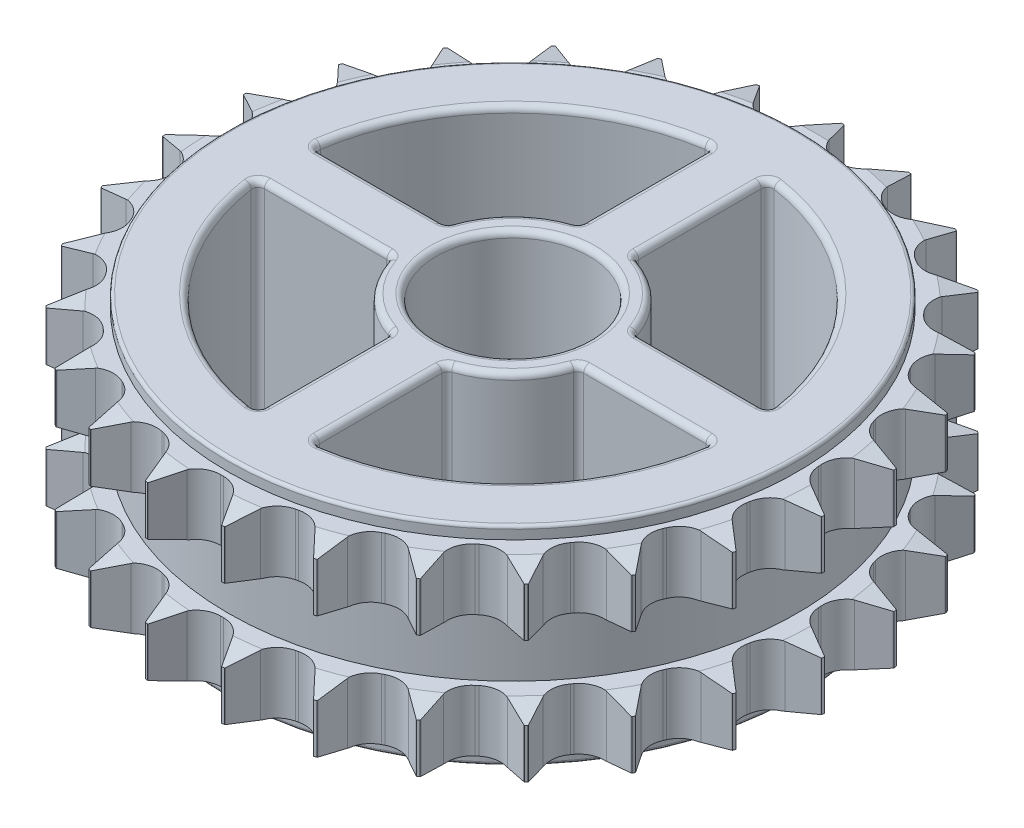
SolidWorks part; units mm, degrees
ref_plane "Front Plane" through (0, 0, 0) normal (0, 0, 1) x (1, 0, 0)
ref_plane "Top Plane" through (0, 0, 0) normal (0, 1, 0) x (1, 0, 0)
ref_plane "Right Plane" through (0, 0, 0) normal (1, 0, 0) x (0, 0, -1)
sketch "Sketch1" plane through (0, 0, 0) normal (0, 1, 0) x (1, 0, 0)
  line L0 (3, 47.4052) -> (0, 54.5)
  line L1 (0, 54.5) -> (-3, 47.4052)
  line L2 (0, 54.5) -> (0, 47.5) construction
  line L3 (-3, 47.4052) -> (0, 47.5) construction
  line L4 (0, 47.5) -> (3, 47.4052) construction
  line L5 (-3, 47.4052) -> (0, 47.5) construction
  line L6 (0, 47.5) -> (3, 47.4052) construction
  line L7 (13.8515, 45.4355) -> (12.5686, 53.0309)
  line L8 (12.5686, 53.0309) -> (8.0132, 46.8192)
  line L9 (23.9563, 41.0164) -> (24.4596, 48.703)
  line L10 (24.4596, 48.703) -> (18.5945, 43.7092)
  line L11 (32.7696, 34.3861) -> (35.0319, 41.7494)
  line L12 (35.0319, 41.7494) -> (28.1733, 38.2428)
  line L13 (39.8163, 25.902) -> (43.7157, 32.5451)
  line L14 (43.7157, 32.5451) -> (36.2333, 30.7148)
  line L15 (44.7164, 16.0216) -> (50.0428, 21.5863)
  line L16 (50.0428, 21.5863) -> (42.3399, 21.5309)
  line L17 (47.2059, 5.2774) -> (53.672, 9.4638)
  line L18 (53.672, 9.4638) -> (46.164, 11.1862)
  line L19 (47.1505, -5.7513) -> (54.4078, -3.1689)
  line L20 (54.4078, -3.1689) -> (47.4994, 0.2386)
  line L21 (44.5532, -16.4699) -> (52.2104, -15.6308)
  line L22 (52.2104, -15.6308) -> (46.2741, -10.722)
  line L23 (39.5541, -26.3007) -> (47.1984, -27.25)
  line L24 (47.1984, -27.25) -> (42.5541, -21.1045)
  line L25 (32.4225, -34.7135) -> (39.6419, -37.4002)
  line L26 (39.6419, -37.4002) -> (36.54, -30.3493)
  line L27 (23.5431, -41.255) -> (29.9482, -45.5341)
  line L28 (29.9482, -45.5341) -> (28.556, -37.9579)
  line L29 (13.3944, -45.5723) -> (18.6401, -51.2132)
  line L30 (18.6401, -51.2132) -> (19.0326, -43.5202)
  line L31 (2.5237, -47.4329) -> (6.3271, -54.1315)
  line L32 (6.3271, -54.1315) -> (8.4831, -46.7364)
  line L33 (-8.4831, -46.7364) -> (-6.3271, -54.1315)
  line L34 (-6.3271, -54.1315) -> (-2.5237, -47.4329)
  line L35 (-19.0326, -43.5202) -> (-18.6401, -51.2132)
  line L36 (-18.6401, -51.2132) -> (-13.3944, -45.5723)
  line L37 (-28.556, -37.9579) -> (-29.9482, -45.5341)
  line L38 (-29.9482, -45.5341) -> (-23.5431, -41.255)
  line L39 (-36.54, -30.3493) -> (-39.6419, -37.4002)
  line L40 (-39.6419, -37.4002) -> (-32.4225, -34.7135)
  line L41 (-42.5541, -21.1045) -> (-47.1984, -27.25)
  line L42 (-47.1984, -27.25) -> (-39.5541, -26.3007)
  line L43 (-46.2741, -10.722) -> (-52.2104, -15.6308)
  line L44 (-52.2104, -15.6308) -> (-44.5532, -16.4699)
  line L45 (-47.4994, 0.2386) -> (-54.4078, -3.1689)
  line L46 (-54.4078, -3.1689) -> (-47.1505, -5.7513)
  line L47 (-46.164, 11.1862) -> (-53.672, 9.4638)
  line L48 (-53.672, 9.4638) -> (-47.2059, 5.2774)
  line L49 (-42.3399, 21.5309) -> (-50.0428, 21.5863)
  line L50 (-50.0428, 21.5863) -> (-44.7164, 16.0216)
  line L51 (-36.2333, 30.7148) -> (-43.7157, 32.5451)
  line L52 (-43.7157, 32.5451) -> (-39.8163, 25.902)
  line L53 (-28.1733, 38.2428) -> (-35.0319, 41.7494)
  line L54 (-35.0319, 41.7494) -> (-32.7696, 34.3861)
  line L55 (-18.5945, 43.7092) -> (-24.4596, 48.703)
  line L56 (-24.4596, 48.703) -> (-23.9563, 41.0164)
  line L57 (-8.0132, 46.8192) -> (-12.5686, 53.0309)
  line L58 (-12.5686, 53.0309) -> (-13.8515, 45.4355)
  line L59 (0, 16) -> (0, 37.5) construction
  line L60 (-4.5, 37.229) -> (-4.5, 15.3542)
  line L61 (4.5, 37.229) -> (4.5, 15.3542)
  line L62 (37.229, -4.5) -> (15.3542, -4.5)
  line L63 (37.229, 4.5) -> (15.3542, 4.5)
  line L64 (-4.5, -37.229) -> (-4.5, -15.3542)
  line L65 (4.5, -37.229) -> (4.5, -15.3542)
  line L66 (-37.229, 4.5) -> (-15.3542, 4.5)
  line L67 (-37.229, -4.5) -> (-15.3542, -4.5)
  line L69 (-1.7, 1.3964) -> (-1.7, -1.3964)
  circle A0 centre (0, 0) radius 47.5
  circle A1 centre (0, 0) radius 37.5
  circle A2 centre (0, 0) radius 5
  circle A3 centre (0, 0) radius 2.2
  circle A4 centre (0, 0) radius 16
  circle A5 centre (0, 0) radius 46.5
  point P88 (0, 0)
  point P111 (0, 0)
  dimension "D1" = 95
  dimension "D5" = 75
  dimension "D6" = 10
  dimension "D7" = 4.4
  dimension "D8" = 32
  dimension "D9" = 4
  dimension "D11" = 0.5
  dimension "D12" = 1
  dimension "D2" = 7
  dimension "D3" = 3
  dimension "D10" = 9
  dimension "D4" = 27
extrude "Boss-Extrude2" add sketch "Sketch1" along normal blind 10 from offset 2 contours A2 A3 | L69 A3 | A4 A2 | A4 L62 A1 L63 | A4 L64 A1 L65 | A4 L66 A1 L67 | A4 L61 A1 L60 | A5 A1 | A0 | L69 A3 region at (5.4988, 0, -47.0454) region at (0, 0, -26.5974) region at (0, 0, -15.5475) region at (-26.5974, 0, 0) region at (26.5974, 0, 0) region at (0, 0, 26.5974) region at (0.1274, 0, 0) region at (-1.9021, 0, 0) region at (-4.8586, 0, 0) region at (-45.1848, 0, 0)
extrude "Boss-Extrude3" add sketch "Sketch1<7>" along normal blind 22 contours L69 A3 | A5 A1 | A4 A2 | A2 A3 | A4 L66 A1 L67 | A4 L64 A1 L65 | A4 L62 A1 L63 | A4 L61 A1 L60 | A3 region at (0, 0, -26.5974) region at (0, 0, -15.5475) region at (-26.5974, 0, 0) region at (26.5974, 0, 0) region at (0, 0, 26.5974) region at (-1.9021, 0, 0) region at (-4.8586, 0, 0) region at (-45.1848, 0, 0)
sketch "Sketch1<7>" plane through (0, 0, 0) normal (0, 1, 0) x (1, 0, 0) same geometry as "Sketch1"
extrude "Boss-Extrude4" add sketch "Sketch1<8>" along normal blind 10 from surface contours A4 A2 | A2 A3 | L69 A3 | A4 L62 A1 L63 | A4 L64 A1 L65 | A4 L66 A1 L67 | A4 L61 A1 L60 | A5 A1 | A0 region at (5.4988, 0, -47.0454) region at (0, 0, -26.5974) region at (0, 0, -15.5475) region at (-26.5974, 0, 0) region at (26.5974, 0, 0) region at (0, 0, 26.5974) region at (-1.9021, 0, 0) region at (-4.8586, 0, 0) region at (-45.1848, 0, 0) starting at face at (-17.1554, 22, 17.1554)
sketch "Sketch1<8>" plane through (0, 0, 0) normal (0, 1, 0) x (1, 0, 0) same geometry as "Sketch1"
extrude "Boss-Extrude6" add sketch "Sketch1<10>" along normal blind 10 from offset 2 contours A0 L57 L58 region at (-11.4875, 0, -48.4696)
sketch "Sketch1<10>" plane through (0, 0, 0) normal (0, 1, 0) x (1, 0, 0) same geometry as "Sketch1"
extrude "Boss-Extrude7" add sketch "Sketch1<12>" along normal blind 10 from surface contours A0 L57 L58 region at (-11.4875, 0, -48.4696) starting at face at (0, 22, 47.5)
sketch "Sketch1<12>" plane through (0, 0, 0) normal (0, 1, 0) x (1, 0, 0) same geometry as "Sketch1"
fillet "Fillet1" radius 4 4 edges at (-13.8515, 7, -45.4355) (-8.0132, 7, -46.8192) (-13.8515, 27, -45.4355) (-8.0132, 27, -46.8192)
fillet "Fillet2" radius 0.3 2 edges at (-12.5686, 7, -53.0309) (-12.5686, 27, -53.0309)
pattern_circular "CirPattern1" count 27 over 360 about axis through (0, 32, 0) along (0, 1, 0) of "Fillet2", "Fillet1", "Boss-Extrude7", "Boss-Extrude6"
sketch "Sketch3" plane through (0, 32, 0) normal (0, 1, 0) x (1, 0, 0)
  circle A0 centre (0, 0) radius 2.5
sketch "Sketch4" plane through (0, 32, 0) normal (0, 1, 0) x (1, 0, 0)
  circle A0 centre (0, 0) radius 0.5
  dimension "D1" = 1
sketch "Sketch6" plane through (0, 32, 0) normal (0, 1, 0) x (1, 0, 0)
  line L0 (-15.3542, 4.5) -> (-37.229, 4.5)
  line L1 (-15.3542, -4.5) -> (-37.229, -4.5)
  line L2 (4.5, 15.3542) -> (4.5, 37.229)
  line L3 (-4.5, 15.3542) -> (-4.5, 37.229)
  line L4 (15.3542, -4.5) -> (37.229, -4.5)
  line L5 (15.3542, 4.5) -> (37.229, 4.5)
  line L6 (-4.5, -15.3542) -> (-4.5, -37.229)
  line L7 (4.5, -15.3542) -> (4.5, -37.229)
  circle A0 centre (0, 0) radius 16
  circle A1 centre (0, 0) radius 46.5
  circle A2 centre (0, 0) radius 37.5
  circle A3 centre (0, 0) radius 16
  circle A4 centre (0, 0) radius 16
  circle A5 centre (0, 0) radius 16
  point P31 (0, 0)
  dimension "D1" = 93
  dimension "D2" = 32
  dimension "D3" = 4
extrude "Boss-Extrude12" add sketch "Sketch6" along normal blind 2 contours L2 A2 L3 A0 | A1 A2 | L0 A2 L1 A0 | L6 A2 L7 A0 | A0 | L4 A2 L5 A0 region at (-26.5974, 32, 0) region at (0, 32, 0) region at (0, 32, -26.5974) region at (0, 32, 26.5974) region at (26.5974, 32, 0) region at (-45.1848, 32, 0)
fillet "Fillet9" radius 0.5 2 edges at (0, 34, 46.5) (0, 0, 46.5)
sketch "Sketch7" plane through (0, 34, 0) normal (0, 1, 0) x (1, 0, 0)
  line L0 (0, 0) -> (0, 5.8384) construction
  line L1 (0, 0) -> (-4.8311, 0) construction
  circle A1 centre (-8, 0) radius 1.5
  circle A2 centre (0, 8) radius 1.5
  circle A3 centre (8, 0) radius 1.5
  circle A4 centre (0, -8) radius 1.5
  point P18 (0, 0)
  dimension "D2" = 3
  dimension "D1" = 90
  dimension "D3" = 8
  dimension "D4" = 4
extrude "Cut-Extrude1" cut sketch "Sketch7" against normal up to next
sketch "Sketch10" plane through (0, 34, 0) normal (0, 1, 0) x (1, 0, 0)
  circle A0 centre (0, 0) radius 12.5
  dimension "D1" = 25
extrude "Cut-Extrude2" cut sketch "Sketch10" against normal offset from surface (21 mm away) 13 up to face at (-8, 0, 1.5)
fillet "Fillet17" radius 1 44 edges at (15.3542, 17, -4.5) (37.229, 17, -4.5) (-4.5, 17, 37.229) (-4.5, 17, 15.3542) (-15.3542, 17, 4.5) (-37.229, 17, 4.5) (-37.229, 17, -4.5) (-15.3542, 17, -4.5) (-4.5, 17, -15.3542) (-4.5, 17, -37.229) (4.5, 17, -37.229) (4.5, 17, -15.3542) (4.5, 17, 15.3542) (4.5, 17, 37.229) (37.229, 17, 4.5) (15.3542, 17, 4.5) (-11.3137, 34, 11.3137) (-26.5165, 34, -26.5165) (-11.3137, 0, 11.3137) (26.5165, 0, 26.5165) (-11.3137, 34, -11.3137) (-11.3137, 0, -11.3137) (11.3137, 34, -11.3137) (26.5165, 34, -26.5165) (11.3137, 0, -11.3137) (11.3137, 34, 11.3137) (11.3137, 0, 11.3137) (26.2916, 34, -4.5) (26.2916, 0, -4.5) (-4.5, 34, 26.2916) (-4.5, 0, 26.2916) (-26.2916, 34, 4.5) (-26.2916, 0, 4.5) (-26.2916, 34, -4.5) (-26.2916, 0, -4.5) (-4.5, 34, -26.2916) (-4.5, 0, -26.2916) (4.5, 34, -26.2916) (4.5, 0, -26.2916) (4.5, 34, 26.2916) (4.5, 0, 26.2916) (26.2916, 34, 4.5) (26.2916, 0, 4.5) (0, 34, 12.5)
sketch "Sketch11" plane through (0, 0, 0) normal (0, 0, 1) x (1, 0, 0)
  line L0 (-49.4165, 12) -> (-53.7394, 12) construction
  line L1 (-53.7394, 2) -> (-49.4165, 2) construction
  line L2 (-49.4165, 2) -> (-49.4165, 12) construction
  line L3 (-53.7394, 12) -> (-53.9388, 12) construction
  line L4 (-53.7715, 12) -> (-53.7715, 2) construction
  line L5 (-53.9388, 2) -> (-53.7394, 2) construction
  line L6 (-53.7394, 32) -> (-53.9388, 32) construction
  line L7 (-53.7715, 32) -> (-53.7715, 22) construction
  line L8 (-53.9388, 22) -> (-53.7394, 22) construction
  line L9 (-49.4165, 32) -> (-53.7394, 32) construction
  line L10 (-53.7394, 22) -> (-49.4165, 22) construction
  line L11 (-49.4165, 22) -> (-49.4165, 32) construction
  line L13 (-49.4165, 12) -> (-53.7394, 12)
  line L14 (-53.7394, 2) -> (-49.4165, 2)
  line L15 (-49.4165, 2) -> (-49.4165, 12)
  line L16 (-53.7394, 12) -> (-53.9388, 12)
  line L17 (-53.7715, 12) -> (-53.7715, 2)
  line L18 (-53.9388, 2) -> (-53.7394, 2)
  line L19 (-53.7394, 32) -> (-53.9388, 32)
  line L20 (-53.7715, 32) -> (-53.7715, 22)
  line L21 (-53.9388, 22) -> (-53.7394, 22)
  line L22 (-49.4165, 32) -> (-53.7394, 32)
  line L23 (-53.7394, 22) -> (-49.4165, 22)
  line L24 (-49.4165, 22) -> (-49.4165, 32)
  line L25 (-53.9388, 32) -> (-53.9388, 22)
  line L26 (-53.9388, 12) -> (-53.9388, 2) construction
  line L27 (-53.9388, 12) -> (-53.9388, 2)
  line L28 (-53.9388, 22) -> (-53.9388, 12) construction
  line L29 (-53.9388, 17) -> (-47.598, 17) construction
  line L30 (-52.955, 27) -> (-56.5762, 27) construction
  line L31 (-49.4165, 32) -> (-53.9388, 31)
  line L32 (-49.4165, 22) -> (-53.9388, 23)
  line L33 (-49.4165, 12) -> (-53.9388, 11)
  line L34 (-49.4165, 2) -> (-53.9388, 3)
  line L35 (0, 27) -> (0, 33.2542) construction
  line L36 (-53.9388, 32) -> (-54.2683, 32)
  line L37 (-53.9388, 31) -> (-54.2683, 31)
  line L38 (-53.9388, 31) -> (-53.9388, 23)
  line L39 (-53.9388, 23) -> (-54.2683, 23)
  line L40 (-54.2683, 31) -> (-54.2683, 23)
  line L41 (-54.2683, 32) -> (-54.2683, 31)
  line L42 (-54.2683, 23) -> (-54.2683, 22)
  line L43 (-54.2683, 22) -> (-53.9388, 22)
  line L45 (-53.9388, 12) -> (-54.2683, 12)
  line L46 (-53.9388, 12) -> (-53.9388, 2)
  line L47 (-53.9388, 2) -> (-54.2683, 2)
  line L48 (-54.2683, 12) -> (-54.2683, 2)
  point P7 (-53.9388, 17)
  point P20 (-53.9388, 27)
  dimension "D1" = 1
revolve "Cut-Revolve1" cut sketch "Sketch11" angle 360 about L35 region at (-52.3198, 11.679, 0) region at (-52.3198, 2.321, 0) region at (-53.8557, 11.5092, 0) region at (-53.8557, 2.4908, 0) region at (-54.1035, 7, 0) region at (-52.3198, 31.679, 0) region at (-53.8557, 31.5092, 0) region at (-54.1035, 31.5, 0) region at (-52.3198, 22.321, 0) region at (-54.1035, 27, 0) region at (-53.8557, 22.4908, 0) region at (-54.1035, 22.5, 0)
